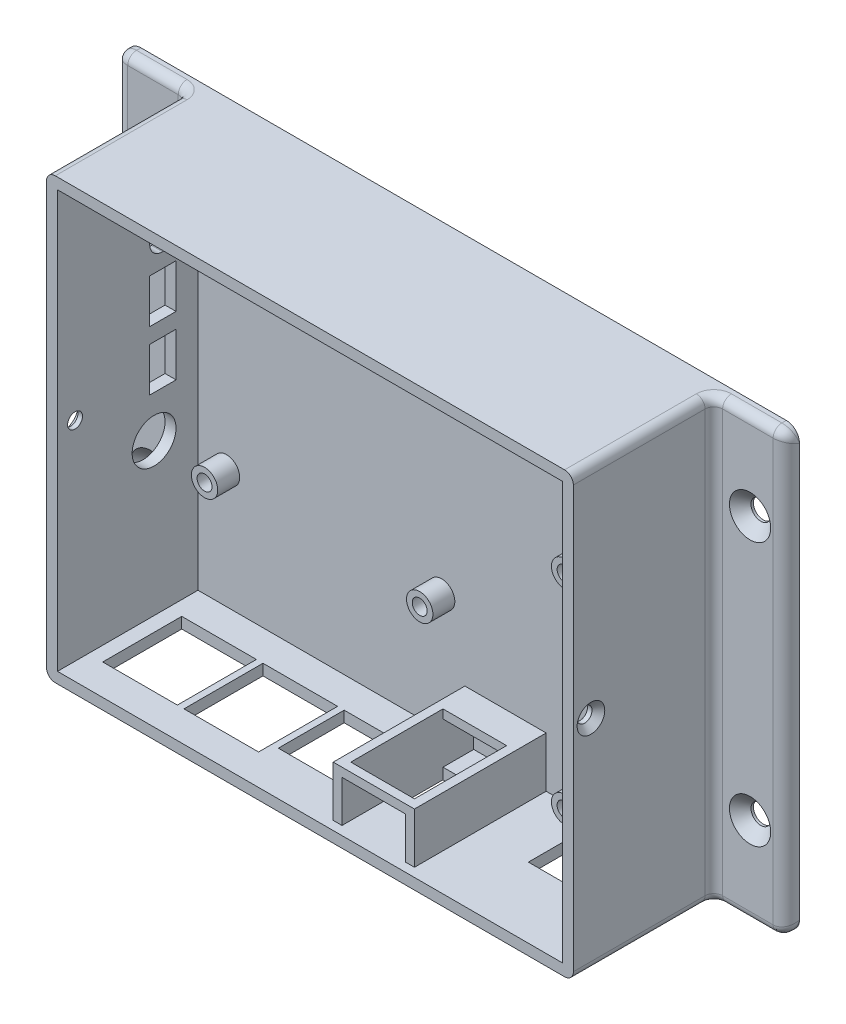
SolidWorks part; units mm, degrees
ref_plane "Přední rovina" through (0, 0, 0) normal (0, 0, 1) x (1, 0, 0)
ref_plane "Horní rovina" through (0, 0, 0) normal (0, 1, 0) x (1, 0, 0)
ref_plane "Pravá rovina" through (0, 0, 0) normal (1, 0, 0) x (0, 0, -1)
sketch "pudorys" plane through (0, 0, 0) normal (0, 0, 1) x (1, 0, 0)
  line L1 (0, 0) -> (153, 0)
  line L2 (0, 0) -> (0, 100)
  line L3 (0, 100) -> (153, 100)
  line L4 (153, 0) -> (153, 100)
  dimension "D1" = 153
  dimension "D2" = 100
extrude "Přidat vysunutím1" add sketch "pudorys" along normal blind 3
sketch "box" plane through (0, 0, 3) normal (0, 0, 1) x (1, 0, 0)
  line L0 (76.5, 0) -> (76.5, 100)
  line L1 (0, 0) -> (153, 0) construction
  line L2 (153, 100) -> (0, 100) construction
  line L3 (19, 97.5) -> (19, 2.5)
  line L4 (16.5, 100) -> (136.5, 100)
  line L5 (16.5, 100) -> (16.5, 0)
  line L6 (16.5, 0) -> (136.5, 0)
  line L7 (136.5, 100) -> (136.5, 0)
  line L8 (16.5, 100) -> (136.5, 0) construction
  line L9 (16.5, 0) -> (136.5, 100) construction
  line L10 (19, 2.5) -> (134, 2.5)
  line L11 (134, 97.5) -> (134, 2.5)
  line L12 (19, 97.5) -> (134, 97.5)
  point P6 (76.5, 50)
  line M6 (0, 0) -> (153, 0)
  line M8 (153, 100) -> (0, 100)
  dimension "D1" = 120
  dimension "D2" = 2.5
extrude "Přidat vysunutím2" add sketch "box" along normal blind 32 contours L3 L12 L0 L5 L10 M8 M6 | L0 L12 L11 L10 L7 M6 M8 region at (46.5, 1.1662, 3) region at (77.6662, 1.25, 3)
sketch "montazni diry" plane through (0, 0, 3) normal (0, 0, 1) x (1, 0, 0)
  line L0 (0, 0) -> (16.5, 0) construction
  line L1 (16.5, 100) -> (0, 100) construction
  line L2 (153, 100) -> (136.5, 100) construction
  line L3 (136.5, 0) -> (153, 0) construction
  line L5 (8.25, 0) -> (8.25, 80)
  line L10 (144.75, 0) -> (144.75, 100)
  point P0 (8.25, 20)
  point P1 (8.25, 80)
  point P2 (144.75, 20)
  point P3 (144.75, 80)
  dimension "D1" = 20
  dimension "D2" = 20
  dimension "D3" = 20
  dimension "D4" = 20
hole_wizard "Válcové zahloubení pro M4 šrouby s plochou hlavou1" positions "3DSkica1" profile "Skica4" countersink size "M4" standard "ANSI Metric" end condition through all
sketch3d "3DSkica1"
  point P0 (8.25, 20, 3)
  point P3 (8.25, 80, 3)
  point P6 (144.75, 80, 3)
  point P9 (144.75, 20, 3)
sketch "Skica4" plane through (8.25, 20, 3) normal (1, 0, 0) x (0, -1, 0)
  line L0 (0, 0) -> (0, 3)
  line L1 (0, 3) -> (2.25, 3)
  line L2 (2.25, 3) -> (2.25, 2.45)
  line L3 (2.25, 2.45) -> (4.7, 0)
  line L5 (4.7, 0) -> (0, 0)
  line L6 (-2.25, 2.45) -> (-4.7, 0) construction
  line L11 (0, -6.35) -> (0, 107.95) construction
  dimension "Průměr díry skrz" = 4.5
  dimension "Hloubka díry skrz" = 3
  dimension "Průměr blíz. kuž. zahloubení" = 9.4
  dimension "Úhel blíz. kuž. zahloubení" = 90
sketch "montážní body" plane through (0, 0, 3) normal (0, 0, 1) x (1, 0, 0)
  line L0 (19, 2.5) -> (19, 97.5)
  line L1 (19, 2.5) -> (134, 2.5) construction
  line L2 (19, 97.5) -> (19, 2.5) construction
  line L3 (19, 2.5) -> (137.3329, 2.5)
  line L4 (134, 2.5) -> (134, 99.5335)
  circle A0 centre (25.5, 29.5) radius 3
  circle A1 centre (74.5, 29.5) radius 3
  circle A2 centre (25.5, 87.5) radius 3
  circle A3 centre (74.5, 87.5) radius 3
  circle A4 centre (107.5, 52.51) radius 3
  circle A5 centre (130, 52.51) radius 3
  circle A6 centre (107.5, 6.01) radius 3
  circle A7 centre (130, 6.01) radius 3
  point P0 (25.5, 29.5)
  point P8 (25.5, 29.5)
  point P10 (25.5, 87.5)
  point P11 (74.5, 29.5)
  point P12 (74.5, 87.5)
  point P13 (130, 6.01)
  point P17 (107.5, 6.01)
  point P18 (130, 52.51)
  point P19 (107.5, 52.51)
  dimension "D9" = 6
  dimension "D10" = 6
  dimension "D11" = 6
  dimension "D12" = 6
  dimension "D13" = 6
  dimension "D14" = 6
  dimension "D15" = 6
  dimension "D16" = 6
  dimension "D1" = 6.5
  dimension "D2" = 27
  dimension "D3" = 58
  dimension "D4" = 49
  dimension "D5" = 3.51
  dimension "D6" = 4
  dimension "D7" = 22.5
  dimension "D8" = 46.5
extrude "Přidat vysunutím6" add sketch "montážní body" along normal blind 5 contours A0 | A1 | A6 | A7 | A4 | A5 | A2 | A3 | A1 | A0 | A4 | A5 | A6 | A7 region at (25.5, 29.5, 3) region at (74.5, 29.5, 3) region at (25.5, 87.5, 3) region at (74.5, 87.5, 3) region at (107.5, 52.51, 3) region at (130, 52.51, 3) region at (107.5, 6.01, 3) region at (130, 6.01, 3)
hole_wizard "M3.5 díra s vůlí1" positions "3DSkica3" profile "Skica8" hole size "M3.5" standard "ANSI Metric"
sketch3d "3DSkica3"
  line L0 (25.5, 87.5, 8) -> (25.5, 87.5, 3) construction
  line L3 (74.5, 87.5, 8) -> (74.5, 87.5, 3) construction
  line L7 (107.5, 52.51, 8) -> (107.5, 52.51, 3) construction
  line L8 (25.5, 29.5, 8) -> (25.5, 29.5, 3) construction
  line L9 (74.5, 29.5, 8) -> (74.5, 29.5, 3) construction
  line L10 (130, 52.51, 8) -> (130, 52.51, 3) construction
  line L11 (130, 6.01, 8) -> (130, 6.01, 3) construction
  line L12 (107.5, 6.01, 8) -> (107.5, 6.01, 3) construction
  point P0 (25.5, 87.5, 8)
  point P12 (74.5, 87.5, 8)
  point P28 (107.5, 52.51, 8)
  point P33 (25.5, 29.5, 8)
  point P37 (74.5, 29.5, 8)
  point P41 (130, 52.51, 8)
  point P45 (130, 6.01, 8)
  point P49 (107.5, 6.01, 8)
sketch "Skica8" plane through (25.5, 87.5, 8) normal (1, 0, 0) x (0, -1, 0)
  line L0 (0, 0) -> (0, 7.0215)
  line L1 (0, 7.0215) -> (1.7, 6)
  line L2 (1.7, 6) -> (1.7, 0)
  line L5 (1.7, 0) -> (0, 0)
  line L10 (0, 7.0215) -> (-1.7, 6) construction
  line L11 (0, -6.35) -> (0, 107.95) construction
  dimension "Průměr díry" = 3.4
  dimension "Hloubka díry" = 6
  dimension "Úhel vrtání" = 118
sketch "Přední panel" plane through (0, 0, 0) normal (0, -1, 0) x (1, 0, 0)
  line L0 (19, 35) -> (19, 0)
  line L1 (22.3, 28) -> (39.3, 28)
  line L2 (22.3, 28) -> (22.3, 10)
  line L3 (22.3, 10) -> (39.3, 10)
  line L4 (39.3, 28) -> (39.3, 10)
  line L5 (22.3, 28) -> (39.3, 10) construction
  line L6 (22.3, 10) -> (39.3, 28) construction
  line L7 (0, 0) -> (153, 0) construction
  line L9 (16.5, 3) -> (153, 3)
  line L10 (136.5, 3) -> (153, 3) construction
  line L12 (57.8, 10) -> (40.8, 10)
  line L13 (57.8, 10) -> (57.8, 28)
  line L14 (57.8, 28) -> (40.8, 28)
  line L15 (40.8, 10) -> (40.8, 28)
  line L16 (57.8, 10) -> (40.8, 28) construction
  line L17 (57.8, 28) -> (40.8, 10) construction
  line L18 (59.3, 10) -> (77.3, 10)
  line L19 (59.3, 10) -> (59.3, 25)
  line L20 (59.3, 25) -> (77.3, 25)
  line L21 (77.3, 10) -> (77.3, 25)
  line L22 (81.8, 10) -> (96.3, 10)
  line L23 (81.8, 10) -> (81.8, 22.2)
  line L24 (81.8, 22.2) -> (96.3, 22.2)
  line L25 (96.3, 10) -> (96.3, 22.2)
  line L26 (136.5, 3) -> (136.5, 35)
  line L27 (16.5, 35) -> (136.5, 35) construction
  line L28 (134, 35) -> (134, -2.187)
  line L29 (130, -2.187) -> (130, 58.451)
  line L30 (118.75, 19) -> (118.75, 10)
  line L31 (130, 10) -> (107.5, 10)
  line L32 (130, 10) -> (130, 19)
  line L33 (130, 19) -> (107.5, 19)
  line L34 (107.5, 10) -> (107.5, 19)
  line L36 (110.25, 19) -> (127.25, 19)
  line L37 (110.25, 19) -> (110.25, 10)
  line L38 (110.25, 10) -> (127.25, 10)
  line L39 (127.25, 19) -> (127.25, 10)
  line L40 (110.25, 19) -> (127.25, 10) construction
  line L41 (110.25, 10) -> (127.25, 19) construction
  point P0 (30.8, 19)
  point P10 (49.3, 19)
  point P44 (118.75, 14.5)
  dimension "D1" = 17
  dimension "D2" = 18
  dimension "D3" = 11.8
  dimension "D4" = 7
  dimension "D5" = 1.5
  dimension "D6" = 18
  dimension "D7" = 15
  dimension "D8" = 1.5
  dimension "D9" = 14.5
  dimension "D10" = 12.2
  dimension "D11" = 4.5
  dimension "D12" = 17
  dimension "D13" = 2.5
  dimension "D14" = 4
  dimension "D15" = 22.5
  dimension "D16" = 9
  dimension "D17" = 17
extrude "Odebrat vysunutím1" cut sketch "Přední panel" against normal blind 32 contours L4 L1 L2 L3 | L15 L12 L13 L14 | L18 L21 L20 L19 | L22 L25 L24 L23 | L33 L37 L31 L30 | L39 L33 L30 L31 region at (30.8, 0, 19) region at (49.3, 0, 19) region at (68.3, 0, 17.5) region at (89.05, 0, 16.1) region at (123, 0, 14.5) region at (114.5, 0, 14.5)
sketch "boční konektory" plane through (16.5, 0, 0) normal (-1, 0, 0) x (0, 0, 1)
  line L0 (8, 0) -> (8, 100)
  line L1 (35, 100) -> (3, 100) construction
  line L2 (8, 0) -> (8, 2.5)
  line L3 (8, 37) -> (13, 37)
  line L5 (8, 46.5) -> (14, 46.5)
  line L6 (8, 46.5) -> (8, 56.5)
  line L7 (8, 56.5) -> (14, 56.5)
  line L8 (14, 46.5) -> (14, 56.5)
  line L9 (8, 60) -> (14, 60)
  line L10 (8, 60) -> (8, 70)
  line L11 (8, 70) -> (14, 70)
  line L12 (14, 60) -> (14, 70)
  line L13 (10.9, 73.3) -> (11.1, 73.3)
  line L14 (8, 76.2) -> (8, 83.4)
  line L15 (10.9, 86.3) -> (11.1, 86.3)
  line L16 (14, 76.2) -> (14, 83.4)
  circle A0 centre (13, 37) radius 5
  arc A1 (8, 83.4) -> (10.9, 86.3) centre (10.9, 83.4) cw
  arc A2 (10.9, 73.3) -> (8, 76.2) centre (10.9, 76.2) cw
  arc A3 (11.1, 73.3) -> (14, 76.2) centre (11.1, 76.2) ccw
  arc A4 (11.1, 86.3) -> (14, 83.4) centre (11.1, 83.4) cw
  point P23 (8, 86.3)
  point P26 (8, 73.3)
  point P29 (14, 73.3)
  point P32 (14, 86.3)
  point P34 (0, 0)
  dimension "D3" = 10
  dimension "D4" = 10
  dimension "D13" = 2.9
  dimension "D1" = 2.5
  dimension "D2" = 34.5
  dimension "D5" = 6
  dimension "D6" = 9.5
  dimension "D7" = 10
  dimension "D8" = 6
  dimension "D9" = 23
  dimension "D10" = 13
  dimension "D11" = 6
  dimension "D12" = 36.3
  dimension "D14" = 5
extrude "Odebrat vysunutím2" cut sketch "boční konektory" against normal blind 10 contours A4 L15 A1 L0 A2 L13 A3 L16 | L9 L12 L11 L0 | L5 L8 L7 L0 | A0 region at (16.5, 79.8, 11) region at (16.5, 65, 11) region at (16.5, 51.5, 11) region at (16.5, 41.8586, 13)
sketch "Skica10" plane through (0, 0, 0) normal (0, -1, 0) x (1, 0, 0)
  line L0 (64.2198, 31.4342) -> (64.5339, 31.4342)
  line L1 (64.5339, 31.4342) -> (64.5339, 28.2932)
  line L2 (81.9374, 27.9342) -> (96.6276, 27.9342)
  line L3 (64.5339, 28.2932) -> (65.8801, 28.2932)
  line L4 (65.8801, 28.2932) -> (65.8801, 27.9342)
  line L5 (65.8801, 27.9342) -> (64.2198, 27.9342)
  line L6 (59.6129, 27.9342) -> (77.4421, 27.9342)
  line L7 (64.2198, 27.9342) -> (64.2198, 31.4342)
  line L8 (67.8993, 31.4342) -> (69.5147, 27.9342)
  line L9 (69.5147, 27.9342) -> (69.1732, 27.9342)
  line L10 (110.1487, 27.9342) -> (127.599, 27.9342)
  line L11 (0, 0) -> (153, 0)
  line L12 (153, 0) -> (153, 3)
  line L13 (153, 3) -> (136.5, 3)
  line L14 (136.5, 3) -> (136.5, 35)
  line L15 (136.5, 35) -> (16.5, 35)
  line L16 (16.5, 35) -> (16.5, 3)
  line L17 (16.5, 3) -> (0, 3)
  line L18 (0, 3) -> (0, 0)
  line L19 (0, 0) -> (153, 0)
  line L20 (153, 0) -> (153, 3)
  line L21 (153, 3) -> (136.5, 3)
  line L22 (136.5, 3) -> (136.5, 35)
  line L23 (136.5, 35) -> (16.5, 35)
  line L24 (16.5, 35) -> (16.5, 3)
  line L25 (16.5, 3) -> (0, 3)
  line L26 (0, 3) -> (0, 0)
  line L27 (69.1732, 27.9342) -> (68.6558, 29.056)
  line L28 (68.6558, 29.056) -> (67.0692, 29.056)
  line L29 (67.0692, 29.056) -> (66.537, 27.9342)
  line L30 (66.537, 27.9342) -> (66.1942, 27.9342)
  line L31 (66.1942, 27.9342) -> (67.8544, 31.4342)
  line L32 (67.8544, 31.4342) -> (67.8993, 31.4342)
  line L33 (67.8734, 30.752) -> (67.2396, 29.415)
  line L34 (67.2396, 29.415) -> (68.4904, 29.415)
  line L35 (68.4904, 29.415) -> (67.8734, 30.752)
  line L36 (70.1429, 27.9342) -> (70.1429, 31.4342)
  line L37 (70.1429, 31.4342) -> (70.2088, 31.4342)
  line L38 (70.2088, 31.4342) -> (72.5211, 28.6795)
  line L39 (72.5211, 28.6795) -> (72.5211, 31.4342)
  line L40 (72.5211, 31.4342) -> (72.8352, 31.4342)
  line L41 (72.8352, 31.4342) -> (72.8352, 27.9342)
  line L42 (72.8352, 27.9342) -> (72.7637, 27.9342)
  line L43 (72.7637, 27.9342) -> (70.457, 30.6826)
  line L44 (70.457, 30.6826) -> (70.457, 27.9342)
  line L45 (70.457, 27.9342) -> (70.1429, 27.9342)
  line L46 (84.7953, 27.9342) -> (84.7953, 31.4342)
  line L47 (84.7953, 31.4342) -> (84.8612, 31.4342)
  line L48 (84.8612, 31.4342) -> (87.1735, 28.6795)
  line L49 (87.1735, 28.6795) -> (87.1735, 31.4342)
  line L50 (87.1735, 31.4342) -> (87.4876, 31.4342)
  line L51 (87.4876, 31.4342) -> (87.4876, 27.9342)
  line L52 (87.4876, 27.9342) -> (87.4161, 27.9342)
  line L53 (87.4161, 27.9342) -> (85.1094, 30.6826)
  line L54 (85.1094, 30.6826) -> (85.1094, 27.9342)
  line L55 (85.1094, 27.9342) -> (84.7953, 27.9342)
  line L56 (88.385, 31.4342) -> (90.0902, 31.4342)
  line L57 (90.0902, 31.4342) -> (90.0902, 31.0752)
  line L58 (90.0902, 31.0752) -> (88.6992, 31.0752)
  line L59 (88.6992, 31.0752) -> (88.6992, 29.9983)
  line L60 (88.6992, 29.9983) -> (90.0902, 29.9983)
  line L61 (90.0902, 29.9983) -> (90.0902, 29.6393)
  line L62 (90.0902, 29.6393) -> (88.6992, 29.6393)
  line L63 (88.6992, 29.6393) -> (88.6992, 27.9342)
  line L64 (88.6992, 27.9342) -> (88.385, 27.9342)
  line L65 (88.385, 27.9342) -> (88.385, 31.4342)
  line L66 (93.9492, 30.792) -> (93.6743, 30.5816)
  line L67 (93.6743, 28.7868) -> (93.9492, 28.5785)
  line L68 (116.361, 30.8368) -> (116.0918, 30.5816)
  line L69 (116.2713, 29.2803) -> (115.1046, 29.2803)
  line L70 (115.1046, 29.2803) -> (115.1046, 29.6393)
  line L71 (115.1046, 29.6393) -> (116.5854, 29.6393)
  line L72 (118.7392, 31.4342) -> (120.3546, 27.9342)
  line L73 (120.3546, 27.9342) -> (120.0131, 27.9342)
  line L74 (120.0131, 27.9342) -> (119.4957, 29.056)
  line L75 (119.4957, 29.056) -> (117.9091, 29.056)
  line L76 (117.9091, 29.056) -> (117.3769, 27.9342)
  line L77 (117.3769, 27.9342) -> (117.0341, 27.9342)
  line L78 (117.0341, 27.9342) -> (118.6943, 31.4342)
  line L79 (118.6943, 31.4342) -> (118.7392, 31.4342)
  line L80 (118.7133, 30.752) -> (118.0794, 29.415)
  line L81 (118.0794, 29.415) -> (119.3302, 29.415)
  line L82 (119.3302, 29.415) -> (118.7133, 30.752)
  line L83 (120.5789, 31.0752) -> (120.5789, 31.4342)
  line L84 (120.5789, 31.4342) -> (122.4187, 31.4342)
  line L85 (122.4187, 31.4342) -> (122.4187, 31.0752)
  line L86 (122.4187, 31.0752) -> (121.6559, 31.0752)
  line L87 (121.6559, 31.0752) -> (121.6559, 27.9342)
  line L88 (121.6559, 27.9342) -> (121.3418, 27.9342)
  line L89 (121.3418, 27.9342) -> (121.3418, 31.0752)
  line L90 (121.3418, 31.0752) -> (120.5789, 31.0752)
  line L91 (122.9571, 31.4342) -> (124.9315, 31.4342)
  line L92 (124.9315, 31.4342) -> (124.9315, 31.0752)
  line L93 (124.9315, 31.0752) -> (123.2713, 31.0752)
  line L94 (123.2713, 31.0752) -> (123.2713, 29.9983)
  line L95 (123.2713, 29.9983) -> (124.9315, 29.9983)
  line L96 (124.9315, 29.9983) -> (124.9315, 29.6393)
  line L97 (124.9315, 29.6393) -> (123.2713, 29.6393)
  line L98 (123.2713, 29.6393) -> (123.2713, 28.2932)
  line L99 (123.2713, 28.2932) -> (124.9315, 28.2932)
  line L100 (124.9315, 28.2932) -> (124.9315, 27.9342)
  line L101 (124.9315, 27.9342) -> (122.9571, 27.9342)
  line L102 (122.9571, 27.9342) -> (122.9571, 31.4342)
  spline S0 degree 3 poles (93.6743, 30.5816) (93.6361, 30.6286) (93.5754, 30.6958) (93.4878, 30.7776) (93.4199, 30.8349) (93.3481, 30.8863) (93.2743, 30.9346) (93.1971, 30.9779) (93.0903, 31.0303) (92.9507, 31.085) (92.7132, 31.1474) (92.5276, 31.1656) (92.4025, 31.165) knots 0 0 0 0 0.125475 0.187121 0.248294 0.309295 0.36985 0.430973 0.492456 0.616148 0.740844 1 1 1 1
  spline S1 degree 3 poles (92.4025, 31.165) (92.3326, 31.1659) (92.2286, 31.1584) (92.0922, 31.1382) (91.9925, 31.1161) (91.8949, 31.0881) (91.7988, 31.0547) (91.7056, 31.0134) (91.614, 30.9676) (91.5262, 30.916) (91.4431, 30.8597) (91.3651, 30.7993) (91.2921, 30.7347) (91.2239, 30.666) (91.1611, 30.5927) (91.1039, 30.5148) (91.0512, 30.4335) (91.004, 30.349) (90.9644, 30.2609) (90.9294, 30.1708) (90.9017, 30.0776) (90.8798, 29.9821) (90.8593, 29.8499) (90.8521, 29.7489) (90.853, 29.6807) knots 0 0 0 0 0.087502 0.130463 0.172752 0.215403 0.25765 0.300153 0.343121 0.385925 0.427686 0.468818 0.509492 0.549883 0.58998 0.630405 0.670869 0.711384 0.751627 0.791776 0.832459 0.873319 0.914543 1 1 1 1
  spline S2 degree 3 poles (90.853, 29.6807) (90.8525, 29.5791) (90.8667, 29.429) (90.9123, 29.2361) (90.9625, 29.1007) (91.0244, 28.9708) (91.1027, 28.8486) (91.1933, 28.7322) (91.2976, 28.6243) (91.412, 28.5258) (91.5347, 28.439) (91.6655, 28.3667) (91.8029, 28.3065) (91.9479, 28.2603) (92.1546, 28.2159) (92.3152, 28.2025) (92.4242, 28.2034) knots 0 0 0 0 0.12629 0.186726 0.246146 0.305576 0.365429 0.426326 0.48884 0.551725 0.613919 0.675484 0.737334 0.800229 0.864502 1 1 1 1
  spline S3 degree 3 poles (92.4242, 28.2034) (92.5444, 28.2034) (92.7229, 28.2203) (92.9508, 28.2823) (93.1121, 28.3461) (93.2654, 28.4292) (93.463, 28.5656) (93.5936, 28.6939) (93.6743, 28.7868) knots 0 0 0 0 0.252949 0.374755 0.49594 0.617181 0.740909 1 1 1 1
  spline S4 degree 3 poles (93.9492, 28.5785) (93.9058, 28.521) (93.837, 28.4383) (93.7362, 28.3373) (93.6565, 28.2671) (93.5734, 28.201) (93.4853, 28.1407) (93.3935, 28.0854) (93.2981, 28.0348) (93.1994, 27.9899) (93.0974, 27.9514) (92.9925, 27.9183) (92.8849, 27.891) (92.7741, 27.8698) (92.6213, 27.8505) (92.5048, 27.8439) (92.4263, 27.8444) knots 0 0 0 0 0.123053 0.183475 0.243727 0.304279 0.364863 0.425946 0.487391 0.54922 0.611144 0.673529 0.736961 0.800785 0.866013 1 1 1 1
  spline S5 degree 3 poles (92.4263, 27.8444) (92.3519, 27.8435) (92.2418, 27.8495) (92.0973, 27.8651) (91.9936, 27.8823) (91.8924, 27.9027) (91.7949, 27.9299) (91.6999, 27.9605) (91.608, 27.9964) (91.5189, 28.0369) (91.433, 28.0827) (91.3504, 28.1334) (91.2702, 28.1878) (91.1936, 28.2478) (91.0948, 28.3345) (91.0258, 28.4059) (90.9827, 28.4565) knots 0 0 0 0 0.13775 0.203917 0.26878 0.332414 0.394754 0.45618 0.516996 0.577396 0.637198 0.696999 0.756756 0.816554 0.876948 1 1 1 1
  spline S6 degree 3 poles (90.9827, 28.4565) (90.9102, 28.5413) (90.8127, 28.6771) (90.7096, 28.8734) (90.6472, 29.0268) (90.5985, 29.1868) (90.5525, 29.4123) (90.5385, 29.5867) (90.5389, 29.7045) knots 0 0 0 0 0.247156 0.36878 0.490734 0.613614 0.738958 1 1 1 1
  spline S7 degree 3 poles (90.5389, 29.7045) (90.5388, 29.8283) (90.5545, 30.0118) (90.6114, 30.2473) (90.6707, 30.4135) (90.746, 30.5726) (90.8391, 30.7234) (90.9487, 30.867) (91.0742, 31.001) (91.2117, 31.1235) (91.3591, 31.2313) (91.5158, 31.321) (91.6804, 31.396) (91.8538, 31.4536) (92.1004, 31.5086) (92.2923, 31.5237) (92.4221, 31.5239) knots 0 0 0 0 0.127014 0.187955 0.248014 0.307748 0.368235 0.42947 0.492743 0.556258 0.618217 0.679655 0.741246 0.803415 0.866815 1 1 1 1
  spline S8 degree 3 poles (92.4221, 31.5239) (92.5017, 31.5241) (92.6198, 31.5187) (92.7743, 31.4977) (92.8859, 31.4766) (92.9951, 31.4504) (93.1009, 31.4162) (93.204, 31.3772) (93.3037, 31.3322) (93.3996, 31.2818) (93.4917, 31.2263) (93.5791, 31.166) (93.6626, 31.1014) (93.7407, 31.031) (93.841, 30.9318) (93.907, 30.8487) (93.9492, 30.792) knots 0 0 0 0 0.135683 0.201215 0.265682 0.329267 0.392395 0.45507 0.517127 0.57879 0.63974 0.700192 0.759806 0.819628 0.879355 1 1 1 1
  spline S9 degree 3 poles (116.0918, 30.5816) (115.9977, 30.6744) (115.847, 30.8007) (115.626, 30.9362) (115.4563, 31.0181) (115.2849, 31.0834) (115.0606, 31.1449) (114.8901, 31.1654) (114.7779, 31.165) knots 0 0 0 0 0.269043 0.398517 0.5271 0.652283 0.77168 1 1 1 1
  spline S10 degree 3 poles (114.7779, 31.165) (114.7101, 31.1658) (114.6091, 31.1584) (114.476, 31.138) (114.3777, 31.1161) (114.2804, 31.0883) (114.1845, 31.0535) (114.0899, 31.0129) (113.9973, 30.9661) (113.9076, 30.9146) (113.8228, 30.8575) (113.7425, 30.7967) (113.6681, 30.7307) (113.5993, 30.66) (113.5344, 30.5859) (113.4756, 30.5065) (113.4225, 30.4231) (113.3751, 30.3373) (113.3333, 30.2499) (113.2982, 30.1612) (113.2704, 30.071) (113.2475, 29.9801) (113.2259, 29.8566) (113.2208, 29.7624) (113.22, 29.6996) knots 0 0 0 0 0.085571 0.127719 0.170068 0.212787 0.255482 0.298877 0.342861 0.386528 0.429532 0.471886 0.513729 0.555082 0.596535 0.63812 0.679822 0.721331 0.761888 0.802199 0.841806 0.88106 0.920633 1 1 1 1
  spline S11 degree 3 poles (113.22, 29.6996) (113.2207, 29.6352) (113.2258, 29.5384) (113.2498, 29.4119) (113.2738, 29.3183) (113.3038, 29.2256) (113.3411, 29.1343) (113.3854, 29.0443) (113.4366, 28.9565) (113.4928, 28.871) (113.5558, 28.7904) (113.6226, 28.7137) (113.6959, 28.6427) (113.7731, 28.5753) (113.8566, 28.5134) (113.9448, 28.456) (114.0378, 28.4036) (114.1346, 28.3568) (114.2339, 28.3151) (114.3359, 28.2809) (114.4402, 28.2529) (114.5465, 28.2301) (114.6929, 28.2101) (114.804, 28.2024) (114.8788, 28.2034) knots 0 0 0 0 0.077882 0.116652 0.155416 0.194618 0.234261 0.274547 0.315667 0.35702 0.398083 0.439098 0.479833 0.521274 0.562841 0.605292 0.648409 0.691727 0.735149 0.778369 0.821661 0.865524 0.909731 1 1 1 1
  spline S12 degree 3 poles (114.8788, 28.2034) (114.9679, 28.2035) (115.0996, 28.2125) (115.2701, 28.2434) (115.3904, 28.2765) (115.5052, 28.3189) (115.6151, 28.3698) (115.7192, 28.4315) (115.8177, 28.5011) (115.9085, 28.5786) (115.9903, 28.6622) (116.062, 28.7516) (116.1245, 28.8462) (116.1761, 28.9467) (116.2335, 29.0894) (116.2597, 29.2031) (116.2713, 29.2803) knots 0 0 0 0 0.138694 0.204918 0.269441 0.332636 0.395302 0.457764 0.520657 0.582852 0.643315 0.70258 0.760908 0.81949 0.878269 1 1 1 1
  spline S13 degree 3 poles (116.5854, 29.6393) (116.5845, 29.5085) (116.5708, 29.316) (116.519, 29.0701) (116.4674, 28.9002) (116.4005, 28.7408) (116.3192, 28.592) (116.222, 28.4546) (116.1125, 28.3276) (115.9896, 28.2143) (115.8566, 28.1147) (115.7134, 28.0308) (115.5599, 27.9625) (115.3969, 27.9093) (115.1611, 27.8576) (114.9767, 27.845) (114.8515, 27.8444) knots 0 0 0 0 0.139493 0.204635 0.267406 0.328446 0.388397 0.447734 0.507392 0.566768 0.625478 0.684067 0.743248 0.804033 0.866499 1 1 1 1
  spline S14 degree 3 poles (114.8515, 27.8444) (114.7735, 27.8446) (114.6582, 27.8497) (114.507, 27.8664) (114.3983, 27.8849) (114.2924, 27.9077) (114.1897, 27.9367) (114.0901, 27.9704) (113.9931, 28.0087) (113.8999, 28.0531) (113.8098, 28.1024) (113.7226, 28.1564) (113.6386, 28.216) (113.5576, 28.2808) (113.4533, 28.3748) (113.381, 28.4524) (113.335, 28.5063) knots 0 0 0 0 0.136557 0.202094 0.266464 0.329769 0.391879 0.453271 0.514115 0.57439 0.634142 0.693923 0.754152 0.81447 0.875661 1 1 1 1
  spline S15 degree 3 poles (113.335, 28.5063) (113.2654, 28.5894) (113.1711, 28.7207) (113.0713, 28.9096) (113.0109, 29.0552) (112.9638, 29.2059) (112.9181, 29.4152) (112.9068, 29.577) (112.9059, 29.6856) knots 0 0 0 0 0.253668 0.376738 0.499344 0.621999 0.745699 1 1 1 1
  spline S16 degree 3 poles (112.9059, 29.6856) (112.9049, 29.7674) (112.9138, 29.8893) (112.9387, 30.0493) (112.9657, 30.1664) (112.9998, 30.2812) (113.0424, 30.394) (113.0919, 30.5047) (113.1495, 30.6126) (113.2136, 30.7162) (113.2831, 30.8151) (113.3592, 30.9076) (113.4404, 30.9948) (113.5278, 31.0756) (113.6205, 31.1508) (113.7187, 31.2204) (113.8227, 31.2834) (113.9308, 31.3399) (114.0428, 31.3895) (114.1588, 31.4305) (114.2778, 31.4653) (114.4007, 31.491) (114.5706, 31.5163) (114.7007, 31.5249) (114.7884, 31.5239) knots 0 0 0 0 0.083544 0.124643 0.165303 0.206171 0.246971 0.288329 0.329987 0.371797 0.412738 0.453459 0.494001 0.534381 0.574952 0.615892 0.65725 0.699007 0.740486 0.782325 0.824567 0.867041 0.9105 1 1 1 1
  spline S17 degree 3 poles (114.7884, 31.5239) (114.8602, 31.5237) (114.9674, 31.5186) (115.1087, 31.5016) (115.2124, 31.4844) (115.3144, 31.4609) (115.4147, 31.4329) (115.5137, 31.4002) (115.6109, 31.3612) (115.7071, 31.3169) (115.8027, 31.2671) (115.8975, 31.2109) (115.9915, 31.1481) (116.0855, 31.0798) (116.2105, 30.9774) (116.3021, 30.8955) (116.361, 30.8368) knots 0 0 0 0 0.122179 0.182216 0.241864 0.30096 0.359969 0.419033 0.478069 0.537993 0.59896 0.661321 0.725248 0.79122 0.858746 1 1 1 1
  dimension "D1" = 0
extrude "Odebrat vysunutím6" cut sketch "Skica10" along normal blind 0.3 and the other way blind 1 contours L32 L31 L6 L29 L28 L27 L8 L35 L34 L33 | L44 L43 L6 L41 L40 L39 L38 L37 L36 | S8 S7 S6 S5 L2 S4 L67 S3 S2 S1 S0 L66 | S17 S16 S15 S14 L10 S13 L71 L70 L69 S12 S11 S10 S9 L68 | L79 L78 L10 L76 L75 L74 L72 L82 L81 L80 | L7 L0 L1 L3 L4 L5 | L48 L49 L50 L51 L52 L53 L54 L55 L46 L47 | L62 L63 L64 L65 L56 L57 L58 L59 L60 L61 | L89 L90 L83 L84 L85 L86 L87 L88 | L97 L98 L99 L100 L101 L102 L91 L92 L93 L94 L95 L96 region at (71.4897, 0, 29.6823) region at (67.0679, 0, 29.6635) region at (91.3722, 0, 28.1791) region at (117.9078, 0, 29.6635) region at (114.836, 0, 27.9856)
sketch "Skica12" plane through (136.5, 0, 0) normal (1, 0, 0) x (0, 0, -1)
  line L0 (-35, 50) -> (-21.0381, 50)
  line L1 (-35, 100) -> (-35, 0) construction
  point P4 (-31, 50)
  dimension "D1" = 4
hole_wizard "Válcové zahloubení pro M3 šrouby s plochou hlavou1" positions "3DSkica4" profile "Skica13" countersink size "M3" standard "ANSI Metric"
sketch3d "3DSkica4"
  point P0 (136.5, 50, 31)
sketch "Skica13" plane through (136.5, 50, 31) normal (0, 1, 0) x (0, 0, -1)
  line L0 (0, 0) -> (0, 7.0215)
  line L1 (0, 7.0215) -> (1.7, 6)
  line L2 (1.7, 6) -> (1.7, 1.45)
  line L3 (1.7, 1.45) -> (3.15, 0)
  line L5 (3.15, 0) -> (0, 0)
  line L6 (-1.7, 1.45) -> (-3.15, 0) construction
  line L10 (0, 7.0215) -> (-1.7, 6) construction
  line L11 (0, -6.35) -> (0, 107.95) construction
  dimension "Průměr díry" = 3.4
  dimension "Hloubka díry" = 6
  dimension "Průměr blíz. kuž. zahloubení" = 6.3
  dimension "Úhel blíz. kuž. zahloubení" = 90
  dimension "Úhel vrtání" = 118
ref_plane "Rovina1" through (76.5, 0, 0) normal (-1, 0, 0) x (0, 0, 1)
mirror "Zrcadlit2" about plane through (76.5, 0, 0) normal (-1, 0, 0) of "Válcové zahloubení pro M3 šrouby s plochou hlavou1"
sketch "Skica14" plane through (0, 2.5, 0) normal (0, 1, 0) x (1, 0, 0)
  line L0 (81.8, -3) -> (81.8, -33)
  line L1 (19, -3) -> (134, -3) construction
  line L2 (81.8, -33) -> (79.8, -33)
  line L3 (79.8, -33) -> (79.8, -3)
  line L4 (79.8, -3) -> (81.8, -3)
  line L5 (89.05, -10) -> (89.05, -22.2)
  line L6 (96.3, -10) -> (81.8, -10) construction
  line L7 (96.3, -22.2) -> (81.8, -22.2) construction
  line L8 (98.3, -3) -> (96.3, -3)
  line L9 (98.3, -33) -> (98.3, -3)
  line L10 (96.3, -33) -> (98.3, -33)
  line L11 (96.3, -3) -> (96.3, -33)
  line M7 (96.3, -10) -> (96.3, -22.2)
  line M9 (81.8, -22.2) -> (81.8, -10)
  line M14 (134, -3) -> (19, -3)
  dimension "D1" = 30
  dimension "D2" = 2
extrude "Přidat vysunutím7" add sketch "Skica14" along normal blind 11.5 contours L11 L10 L9 M14 M7 | L3 L2 L0 M9 M14 region at (80.8, 2.5, 18) region at (97.3, 2.5, 18)
sketch "Skica15" plane through (81.8, 0, 0) normal (1, 0, 0) x (0, 0, -1)
  line L1 (-33, 14) -> (-31, 14)
  line L2 (-33, 14) -> (-33, 12)
  line L3 (-33, 12) -> (-31, 12)
  line L4 (-31, 14) -> (-31, 12)
  line L5 (-3, 14) -> (-10, 14)
  line L6 (-3, 14) -> (-3, 12)
  line L7 (-3, 12) -> (-10, 12)
  line L8 (-10, 14) -> (-10, 12)
  dimension "D1" = 2
  dimension "D2" = 2
  dimension "D3" = 2
  dimension "D4" = 7
extrude "Přidat vysunutím8" add sketch "Skica15" along normal blind 15.1359
fillet "Zaoblit1" radius 2 2 edges at (16.5, 50, 3) (136.5, 50, 3)
fillet "Zaoblit2" radius 2 12 edges at (7.25, 100, 3) (15.9142, 100, 3.5858) (7.25, 0, 3) (15.9142, 0, 3.5858) (145.75, 100, 3) (137.0858, 100, 3.5858) (145.75, 0, 3) (137.0858, 0, 3.5858) (16.5, 100, 20) (16.5, 0, 20) (136.5, 100, 20) (136.5, 0, 20)
fillet "Zaoblit3" radius 3 10 edges at (153, 100, 0.5) (153, 99.4142, 2.4142) (153, 50, 3) (153, 0.5858, 2.4142) (153, 0, 0.5) (0, 100, 0.5) (0, 99.4142, 2.4142) (0, 50, 3) (0, 0.5858, 2.4142) (0, 0, 0.5)
